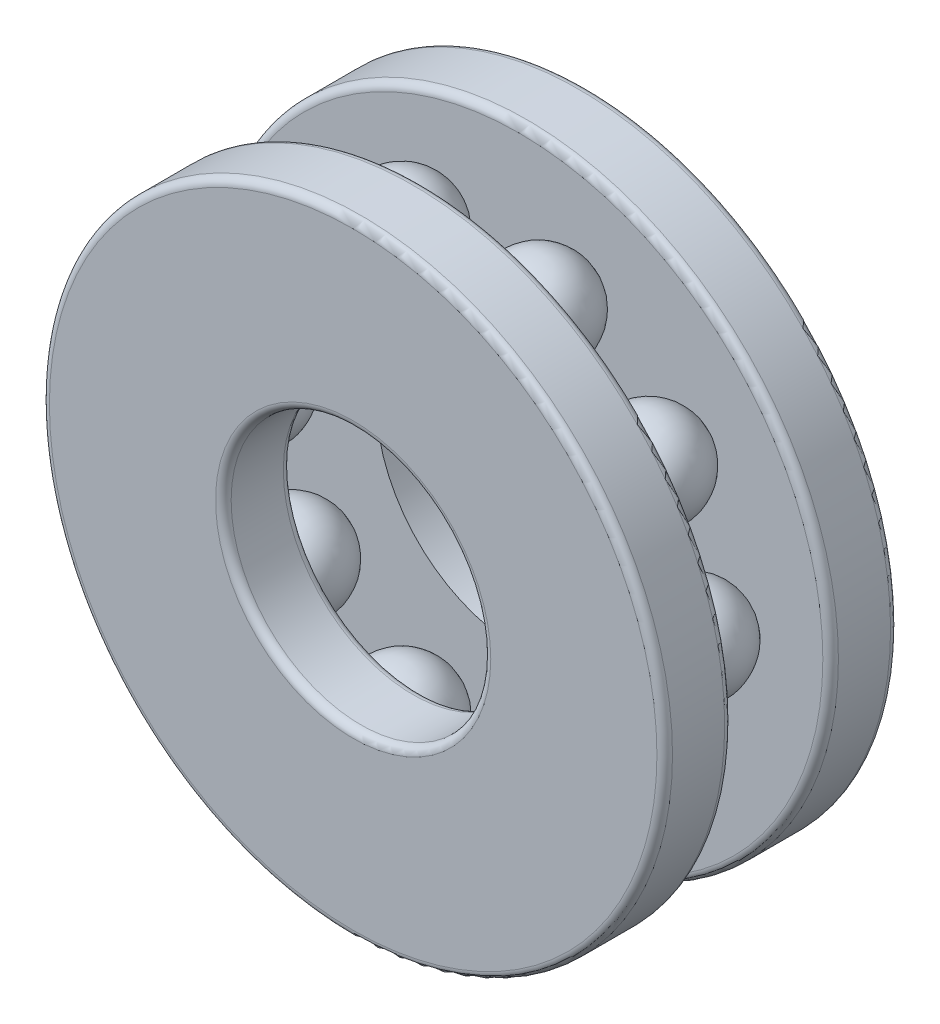
SolidWorks part; units mm, degrees
ref_plane "Front Plane" through (0, 0, 0) normal (0, 0, 1) x (1, 0, 0)
ref_plane "Top Plane" through (0, 0, 0) normal (0, 1, 0) x (1, 0, 0)
ref_plane "Right Plane" through (0, 0, 0) normal (1, 0, 0) x (0, 0, -1)
sketch "S" plane through (0, 0, 0) normal (0, 0, 1) x (1, 0, 0)
  line L0 (-4.5, 0) -> (4.5, 0) construction
  circle A0 centre (0, 0) radius 5 construction
  circle A1 centre (0, 0) radius 12 construction
  circle A2 centre (0, 0) radius 6.4 construction
  circle A3 centre (0, 0) radius 10.6 construction
  circle A4 centre (0, 0) radius 12 construction
  circle A5 centre (0, 0) radius 5.5 construction
  dimension "ID" = 10
  dimension "OD" = 24
  dimension "IDa" = 12.8
  dimension "ODa" = 21.2
  dimension "d1" = 24
  dimension "D1h" = 11
  dimension "B" = 9
ref_axis "Z" through (0, 0, -4.95) along (0, 0, 1)
sketch "ShaftWasherS" plane through (0, 0, 0) normal (0, 1, 0) x (1, 0, 0)
  line L0 (5, -4.5) -> (12, -4.5)
  line L1 (12, -4.5) -> (12, -1.89)
  line L2 (12, -1.89) -> (5, -1.89)
  line L3 (5, -1.89) -> (5, -4.5)
  line L4 (0, -7.75) -> (0, 7.75) construction
  dimension "r1" = 5
  dimension "r2" = 12
  dimension "z1" = 4.5
  dimension "z2" = 1.89
revolve "ShaftWasher" add sketch "ShaftWasherS" angle 360 about L4
sketch "HousingWasherS" plane through (0, 0, 0) normal (0, 1, 0) x (1, 0, 0)
  line L0 (5.5, 1.89) -> (12, 1.89)
  line L1 (12, 1.89) -> (12, 4.5)
  line L2 (12, 4.5) -> (5.5, 4.5)
  line L3 (5.5, 4.5) -> (5.5, 1.89)
  line L4 (0, -7.75) -> (0, 7.75) construction
  dimension "r2" = 12
  dimension "r1" = 5.5
  dimension "z1" = 1.89
  dimension "z2" = 4.5
revolve "HousingWasher" add sketch "HousingWasherS" angle 360 about L4
sketch "BallS" plane through (0, 0, 0) normal (0, 1, 0) x (1, 0, 0)
  line L0 (6.61, 0) -> (10.39, 0)
  arc A0 (6.61, 0) -> (10.39, 0) centre (8.5, 0) ccw
  dimension "r" = 1.89
  dimension "p" = 8.5
revolve "Ball" add sketch "BallS" angle 360 about L0
pattern_circular "BallsPattern" count 10 over 360 about axis through (0, 0, -4.95) along (0, 0, 1) of bodies 103
fillet "F1" radius 0.3 2 edges at (12, 0, -4.5) (12, 0, -1.89)
fillet "F2" radius 0.3 4 edges at (5, 0, 1.89) (12, 0, 1.89) (12, 0, 4.5) (5, 0, 4.5)
equation "\"r1@ShaftWasherS\" = abs(0.5*\"ID@S\")"
equation "\"r2@ShaftWasherS\" = abs(0.5*\"d1@S\")"
equation "\"z1@ShaftWasherS\" = abs(-0.5*\"B@S\")"
equation "\"z2@ShaftWasherS\" = abs(-0.21*\"B@S\")"
equation "\"r1@HousingWasherS\" = abs(0.5*\"D1h@S\")"
equation "\"r2@HousingWasherS\" = abs(0.5*\"OD@S\")"
equation "\"z1@HousingWasherS\" = abs(0.21*\"B@S\")"
equation "\"z2@HousingWasherS\" = abs(0.5*\"B@S\")"
equation "\"r@BallS\" = abs(0.21*\"B@S\")"
equation "\"p@BallS\" = abs(0.25*\"IDa@S\"+0.25*\"ODa@S\")"
equation "\"N@BallsPattern\" = int(2.417*(0.25*\"IDa@S\"+0.25*\"ODa@S\")/(0.21*\"B@S\"))"
equation "\"r_min@F2\" = \"r_min@F1\""
